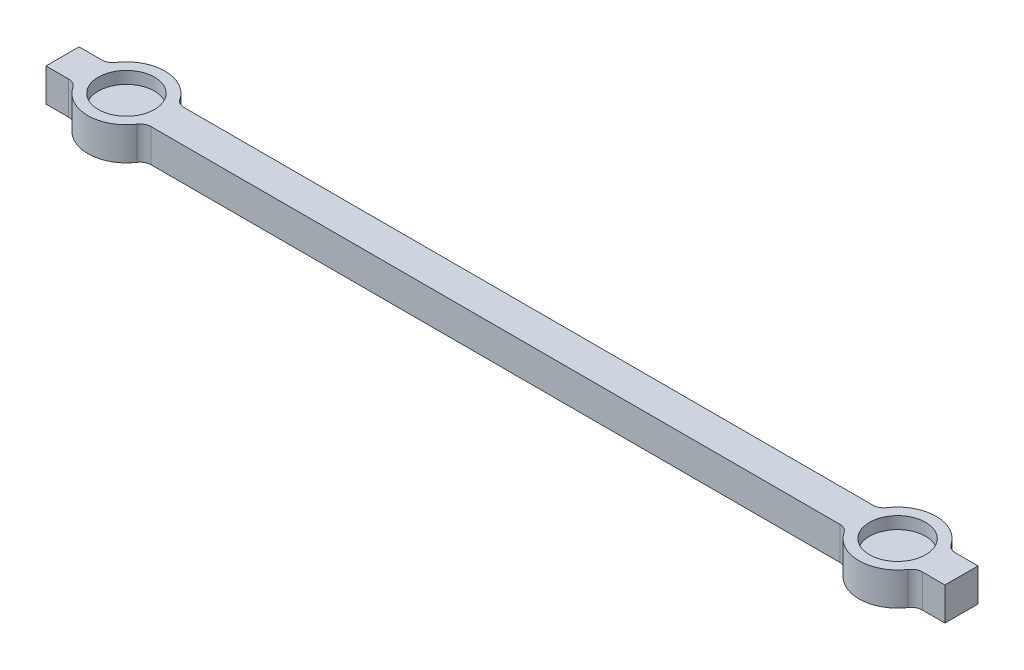
SolidWorks part; units mm, degrees
ref_plane "Front Plane" through (0, 0, 0) normal (0, 0, 1) x (1, 0, 0)
ref_plane "Top Plane" through (0, 0, 0) normal (0, 1, 0) x (1, 0, 0)
ref_plane "Right Plane" through (0, 0, 0) normal (1, 0, 0) x (0, 0, -1)
sketch "Sketch1" plane through (0, 0, 0) normal (0, 1, 0) x (1, 0, 0)
  line L0 (-40.8, 0) -> (40.8, 0) construction
  line L1 (-40.8, 3.5) -> (40.8, 3.5)
  line L2 (-40.8, 3.5) -> (-40.8, -3.5)
  line L3 (-40.8, -3.5) -> (40.8, -3.5)
  line L4 (40.8, 3.5) -> (40.8, -3.5)
  line L5 (-40.8, 3.5) -> (40.8, -3.5) construction
  line L6 (-40.8, -3.5) -> (40.8, 3.5) construction
  line L7 (0, 3.5) -> (0, -3.5) construction
  line L8 (-39.5, 3.5) -> (-39.5, -3.5) construction
  line L10 (40.8, 1.5) -> (-40.8, 1.5)
  line L11 (40.8, 1.5) -> (40.8, -1.5)
  line L12 (40.8, -1.5) -> (-40.8, -1.5)
  line L13 (-40.8, 1.5) -> (-40.8, -1.5)
  line L14 (40.8, 1.5) -> (-40.8, -1.5) construction
  line L15 (40.8, -1.5) -> (-40.8, 1.5) construction
  circle A0 centre (-35, 0) radius 2.5
  circle A1 centre (-35, 0) radius 3.5
  circle A2 centre (35, 0) radius 3.5
  point P0 (0, 0)
  point P15 (-37.5, 0)
  point P16 (0, 0)
  dimension "D3" = 5
  dimension "D1" = 81.6
  dimension "D2" = 7
  dimension "D4" = 1.3
  dimension "D5" = 2
  dimension "D6" = 3
extrude "Base shape" add sketch "Sketch1" along normal blind 3 contours A1 | L10 L13 L12 L11 | A2
sketch "Sketch2" plane through (0, 3, 0) normal (0, 1, 0) x (1, 0, 0)
  circle A0 centre (-35, 0) radius 2.55
  circle A1 centre (35, 0) radius 2.55
  dimension "D1" = 5.1
extrude "Magnet holes" cut sketch "Sketch2" against normal blind 1.1
fillet "Fillet1" radius 1 8 edges at (31.8377, 1.5, -1.5) (-38.1623, 1.5, -1.5) (-31.8377, 1.5, -1.5) (38.1623, 1.5, -1.5) (38.1623, 1.5, 1.5) (31.8377, 1.5, 1.5) (-31.8377, 1.5, 1.5) (-38.1623, 1.5, 1.5)
